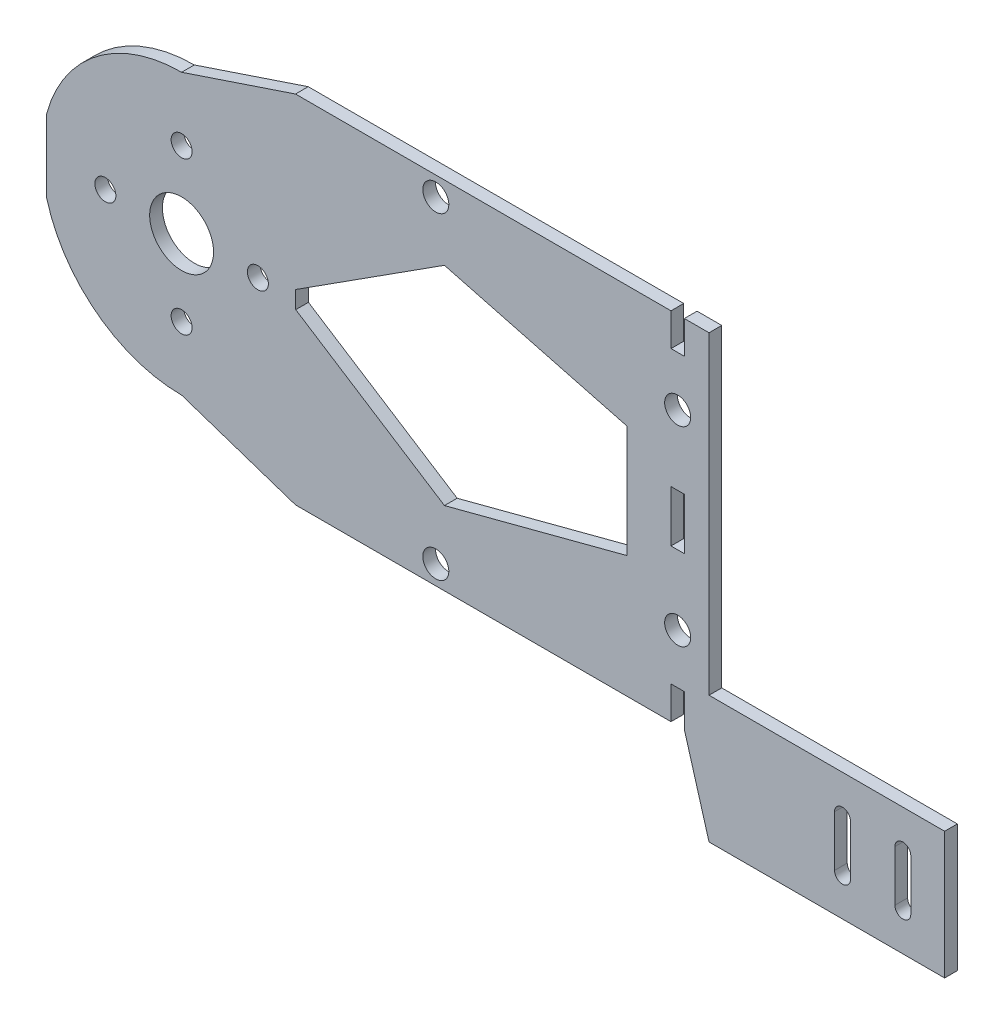
SolidWorks part; units mm, degrees
ref_plane "前视基准面" through (0, 0, 0) normal (0, 0, 1) x (1, 0, 0)
ref_plane "上视基准面" through (0, 0, 0) normal (0, 1, 0) x (1, 0, 0)
ref_plane "右视基准面" through (0, 0, 0) normal (1, 0, 0) x (0, 0, -1)
sketch "草图1" plane through (0, 0, 0) normal (0, 0, 1) x (1, 0, 0)
  line L0 (31.0657, 12.95) -> (31.0657, 17.05) construction
  line L1 (30.0157, 28) -> (32.1157, 28) construction
  line L2 (32.1157, -4.05) -> (30.0157, -4.05)
  line L3 (32.1157, -4.05) -> (32.1157, 4.05)
  line L4 (32.1157, 4.05) -> (30.0157, 4.05)
  line L5 (30.0157, -4.05) -> (30.0157, 4.05)
  line L6 (32.1157, -4.05) -> (30.0157, 4.05) construction
  line L7 (32.1157, 4.05) -> (30.0157, -4.05) construction
  line L8 (32.1157, 28) -> (32.1157, 22.85)
  line L9 (30.0157, 22.85) -> (32.1157, 22.85)
  line L10 (30.0157, 28) -> (30.0157, 22.85)
  line L11 (31.0657, 0) -> (29.7708, 0) construction
  line L12 (30.0157, -28) -> (32.1157, -28) construction
  line L13 (31.0657, -12.95) -> (31.0657, -17.05) construction
  line L14 (30.0157, -28) -> (30.0157, -22.85)
  line L15 (30.0157, -22.85) -> (32.1157, -22.85)
  line L16 (32.1157, -28) -> (32.1157, -22.85)
  line L17 (32.1157, -28) -> (36.001, -28) construction
  line L18 (36.001, -28) -> (36.001, 28) construction
  line L19 (36.001, 28) -> (32.1157, 28)
  line L23 (-46.999, -22.002) -> (-29.075, -28)
  line L25 (-46.999, 22.002) -> (-29.075, 28)
  line L29 (30.0157, -28) -> (-29.075, -28)
  line L30 (-29.075, 28) -> (30.0157, 28)
  line L31 (-29.075, -28) -> (-29.075, 28) construction
  line L41 (31.0657, -15) -> (31.0657, 15) construction
  line L42 (31.0657, 15) -> (-6.999, 25) construction
  line L46 (-6.999, -25) -> (31.0657, -15) construction
  line L47 (-5.6375, -16.3709) -> (23.0657, -8.8302)
  line L48 (23.0657, -8.8302) -> (23.0657, 8.8302)
  line L49 (23.0657, 8.8302) -> (-5.6375, 16.3709)
  line L50 (-5.6375, 16.3709) -> (-29.0397, 1.3748)
  line L51 (-29.0397, 1.3748) -> (-29.0397, -1.3748)
  line L52 (-29.0397, -1.3748) -> (-5.6375, -16.3709)
  line L53 (-82.9583, 0) -> (-46.999, 0) construction
  line L54 (-46.999, 0) -> (77.0107, 0) construction
  line L55 (-68.2364, -5.75) -> (-87.6313, -5.75) construction
  line L56 (-87.6313, -5.75) -> (-87.6313, 5.75) construction
  line L57 (-87.6313, 5.75) -> (-68.2364, 5.75) construction
  line L58 (36.001, -21.4019) -> (73.0775, -21.4019)
  line L59 (73.0775, -21.4019) -> (73.0775, -41.4019)
  line L60 (73.0775, -41.4019) -> (36.001, -41.4019)
  line L61 (36.001, -21.4019) -> (36.001, 28)
  line L62 (36.001, -41.4019) -> (36.001, -28) construction
  line L63 (-37.0397, 5.75) -> (-37.0397, -5.75) construction
  line L64 (-37.0397, -5.75) -> (-6.999, -25) construction
  line L65 (-6.999, 25) -> (-37.0397, 5.75) construction
  line L66 (57.001, -31.4019) -> (66.501, -31.4019) construction
  line L67 (66.501, -27.4019) -> (66.501, -35.4019) construction
  line L70 (57.001, -35.4019) -> (57.001, -27.4019) construction
  line L71 (55.751, -35.4019) -> (55.751, -27.4019)
  line L72 (58.251, -35.4019) -> (58.251, -27.4019)
  line L73 (67.751, -27.4019) -> (67.751, -35.4019)
  line L74 (65.251, -27.4019) -> (65.251, -35.4019)
  line L75 (32.1157, -28) -> (36.001, -41.4019)
  line L76 (-68.2364, -5.75) -> (-68.2364, 5.75)
  circle A0 centre (31.0657, 15) radius 2.05
  circle A1 centre (31.0657, -15) radius 2.05
  circle A3 centre (-46.999, 0) radius 5.025
  circle A6 centre (-46.999, 0) radius 12 construction
  circle A18 centre (-46.999, 0) radius 22.002 construction
  circle A30 centre (-6.999, -25) radius 2.05
  circle A31 centre (-6.999, 25) radius 2.05
  arc A32 (-46.999, -22.002) -> (-68.2364, -5.75) centre (-46.999, 0) cw
  arc A33 (-68.2364, 5.75) -> (-46.999, 22.002) centre (-46.999, 0) cw
  circle A34 centre (-82.9583, 0) radius 2.05 construction
  arc A38 (55.751, -35.4019) -> (58.251, -35.4019) centre (57.001, -35.4019) ccw
  circle A39 centre (-58.999, 0) radius 1.65
  arc A43 (58.251, -27.4019) -> (55.751, -27.4019) centre (57.001, -27.4019) ccw
  arc A44 (67.751, -27.4019) -> (65.251, -27.4019) centre (66.501, -27.4019) ccw
  arc A45 (65.251, -35.4019) -> (67.751, -35.4019) centre (66.501, -35.4019) ccw
  circle A46 centre (-46.999, 12) radius 1.65
  circle A47 centre (-34.999, 0) radius 1.65
  circle A48 centre (-46.999, -12) radius 1.65
  point P4 (31.0657, 0)
  point P71 (66.501, -31.4019)
  point P79 (57.001, -31.4019)
  point P84 (36.001, -34.701)
  dimension "D3" = 10.05
  dimension "D4" = 83
  dimension "D5" = 35.9593
  dimension "D6" = 3.3
  dimension "D7" = 24
  dimension "D8" = 4
  dimension "D9" = 40
  dimension "D11" = 3
  dimension "D14" = 21
  dimension "D19" = 28
  dimension "D21" = 20
  dimension "D13" = 9.5
  dimension "D1" = 8.1
  dimension "D2" = 2.1
  dimension "D10" = 3
  dimension "D12" = 40
  dimension "D15" = 3.8853
  dimension "D16" = 2.1
  dimension "D18" = 30
  dimension "D17" = 8
extrude "凸台-拉伸1" add sketch "草图1" along normal blind 2 contours A33 L57 L56 L55 A32 L23 L29 L14 L15 L16 L75 L60 L59 L58 L61 L19 L8 L9 L10 L30 L25 A45 L74 A44 L73 A43 L72 A38 L71 A39 A34 A31 A30 A3 L2 L5 L4 L3 region at (34.0584, 26.4256, 0)
